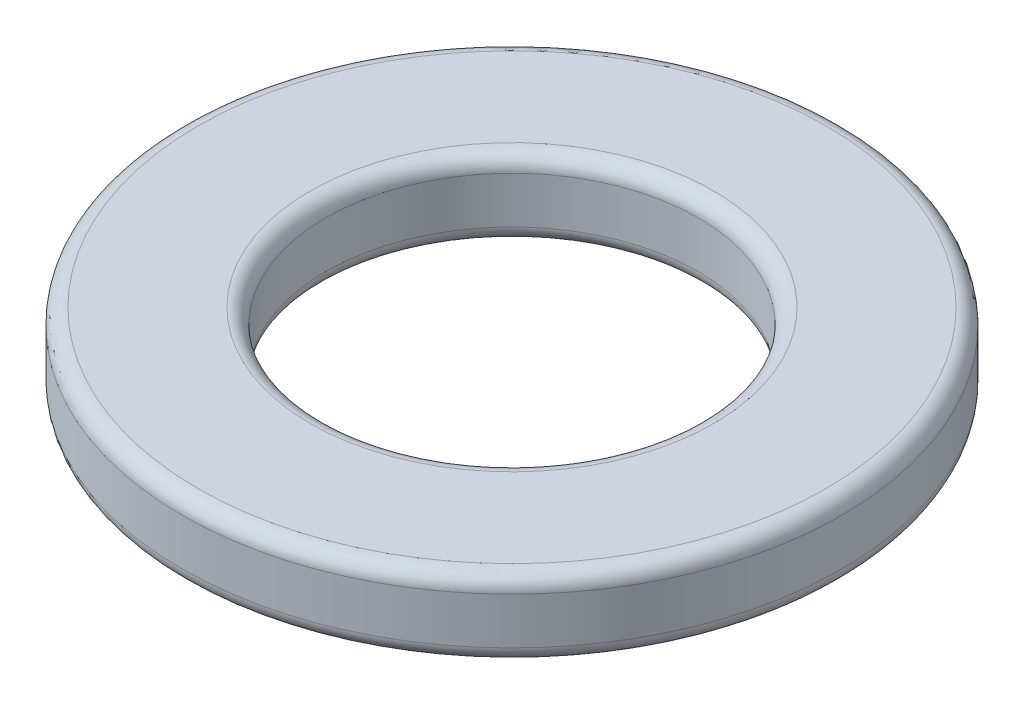
SolidWorks part; units mm, degrees
ref_plane "Front Plane" through (0, 0, 0) normal (0, 0, 1) x (1, 0, 0)
ref_plane "Top Plane" through (0, 0, 0) normal (0, 1, 0) x (1, 0, 0)
ref_plane "Right Plane" through (0, 0, 0) normal (1, 0, 0) x (0, 0, -1)
ref_axis "X Axis" through (-88.99, 0, 0) along (1, 0, 0)
ref_axis "Y Axiz" through (0, 0, 55) along (0, 0, -1)
ref_axis "Z Axis" through (0, 55, 0) along (0, -1, 0)
sketch "Sketch1" plane through (0, 0, 0) normal (0, 1, 0) x (1, 0, 0)
  circle A0 centre (0, 0) radius 2.4
  circle A1 centre (0, 0) radius 4.25
  dimension "D1" = 4.8
  dimension "D2" = 8.5
extrude "Boss-Extrude1" add sketch "Sketch1" along normal blind 1
fillet "Fillet1" radius 0.2 4 edges at (0, 0, 2.4) (0, 0, 4.25) (0, 1, 4.25) (0, 1, 2.4)
